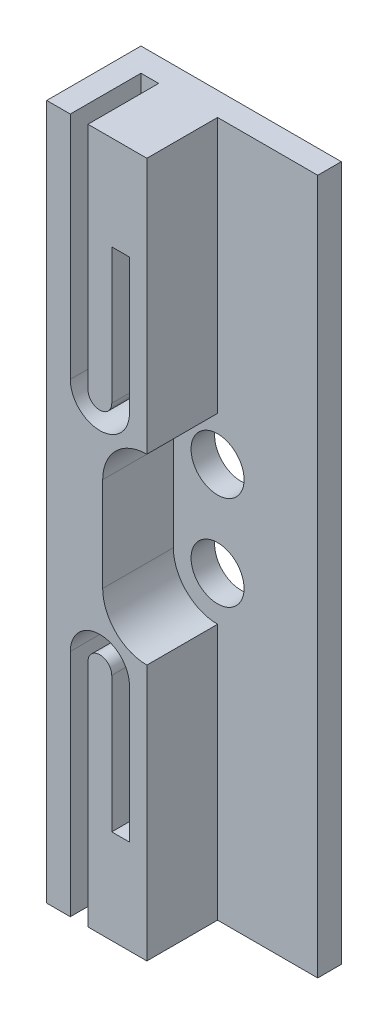
SolidWorks part; units mm, degrees
ref_plane "Plan de face" through (0, 0, 0) normal (0, 0, 1) x (1, 0, 0)
ref_plane "Plan de dessus" through (0, 0, 0) normal (0, 1, 0) x (1, 0, 0)
ref_plane "Plan de droite" through (0, 0, 0) normal (1, 0, 0) x (0, 0, -1)
sketch "Esquisse1" plane through (0, 0, 0) normal (0, 0, 1) x (1, 0, 0)
  line L1 (0, 0) -> (17, 0)
  line L2 (0, 0) -> (0, -59)
  line L3 (0, -59) -> (17, -59)
  line L4 (17, 0) -> (17, -59)
  dimension "D1" = 17
  dimension "D2" = 59
extrude "Boss.-Extru.1" add sketch "Esquisse1" along normal blind 2
sketch "Esquisse2" plane through (0, 0, 2) normal (0, 0, 1) x (1, 0, 0)
  line L0 (0, -59) -> (17, -59) construction
  line L1 (0, 0) -> (8.5, 0)
  line L2 (0, 0) -> (0, -59)
  line L3 (0, -59) -> (8.5, -59)
  line L4 (8.5, 0) -> (8.5, -59)
extrude "Boss.-Extru.2" add sketch "Esquisse2" along normal blind 6
sketch "Esquisse3" plane through (0, 0, 8) normal (0, 0, 1) x (1, 0, 0)
  line L0 (0, -59) -> (8.5, -59) construction
  line L1 (2, -59) -> (3.5, -59)
  line L2 (2, -59) -> (2, 0)
  line L3 (2, 0) -> (3.5, 0)
  line L4 (3.5, -59) -> (3.5, 0)
  line L5 (8.5, 0) -> (0, 0) construction
  line L6 (8.5, -59) -> (8.5, 0) construction
  line L7 (2, -19.5) -> (3.5, -19.5)
  line L8 (5.5199, -51) -> (7.0199, -51)
  line L9 (5.5199, -51) -> (5.5199, -8)
  line L10 (5.5199, -8) -> (7.0199, -8)
  line L11 (7.0199, -51) -> (7.0199, -8)
  line L13 (3.5, -19.5) -> (5.5199, -19.5)
  line L14 (5.5199, -19.5) -> (7.0908, -19.5)
  line L15 (2, -39.5) -> (3.5, -39.5)
  line L16 (3.5, -39.5) -> (5.5199, -39.5)
  line L17 (5.5199, -39.5) -> (7.0199, -39.5)
  arc A0 (2, -19.5) -> (7.0199, -19.5) centre (4.51, -19.5) ccw
  arc A1 (3.5, -19.5) -> (5.5199, -19.5) centre (4.51, -19.5) ccw
  arc A2 (3.5, -39.5) -> (5.5199, -39.5) centre (4.51, -39.5) cw
  arc A3 (2, -39.5) -> (7.0199, -39.5) centre (4.51, -39.5) cw
  point P14 (6.2699, -8)
  line M10 (0, -59) -> (8.5, -59)
  line M12 (8.5, 0) -> (0, 0)
  dimension "D1" = 1.5
  dimension "D2" = 5
  dimension "D3" = 1.5
  dimension "D4" = 8
  dimension "D5" = 8
  dimension "D6" = 20
  dimension "D7" = 11.5
  dimension "D8" = 11.5
extrude "Enlèv. mat.-Extru.1" cut sketch "Esquisse3" against normal blind 6 contours L15 L2 L4 M10 | A3 L15 L4 | A3 L4 A2 L9 | A3 L9 L17 | L17 L9 L8 L11 | L9 L14 L11 L10 | L2 L7 L4 M12 | L7 A0 L4 | A1 L4 A0 L9 | L9 A0 L14 region at (2.75, -49.25, 8) region at (2.8814, -38.5894, 8) region at (4.51, -37.8974, 8) region at (2.75, -9.75, 8) region at (2.8814, -20.4106, 8) region at (6.2699, -45.25, 8) region at (6.1386, -38.5894, 8) region at (4.51, -21.1026, 8) region at (6.1386, -20.4106, 8) region at (6.2699, -13.75, 8)
sketch "Esquisse4" plane through (0, 0, 8) normal (0, 0, 1) x (1, 0, 0)
  line L2 (3.5, -59) -> (8.5, -59) construction
  line L3 (17, -59) -> (17, 0) construction
  line L4 (0, 0) -> (0, -59) construction
  circle A0 centre (8.5, -33.5) radius 2.25
  circle A1 centre (8.5, -25.5) radius 2.25
  point P8 (6, -59)
  dimension "D1" = 4.5
  dimension "D2" = 4.5
  dimension "D3" = 8
  dimension "D4" = 25.5
  dimension "D5" = 17
  dimension "D6" = 8.5
  dimension "D7" = 8.5
extrude "Enlèv. mat.-Extru.2" cut sketch "Esquisse4" against normal blind 14
sketch "Esquisse5" plane through (0, 0, 8) normal (0, 0, 1) x (1, 0, 0)
  line L0 (4.75, -33.5) -> (4.75, -25.5)
  circle A0 centre (8.5, -25.5) radius 3.75
  circle A1 centre (8.5, -33.5) radius 3.75
  arc M1 (8.5, -27.75) -> (8.5, -23.25) centre (8.5, -25.5) cw
  line M2 (8.5, -23.25) -> (8.5, 0)
  line M22 (8.5, -59) -> (8.5, -35.75)
  arc M23 (8.5, -35.75) -> (8.5, -31.25) centre (8.5, -33.5) cw
  line M24 (8.5, -31.25) -> (8.5, -27.75)
  dimension "D1" = 7.5
  dimension "D2" = 7.5
extrude "Enlèv. mat.-Extru.3" cut sketch "Esquisse5" against normal blind 6 contours A1 A0 L0 M24 | A0 M2 M24 M1 | A1 M24 M22 M23 region at (5.8335, -29.5, 8) region at (5.9076, -30.9076, 8) region at (5.9076, -22.9076, 8)
